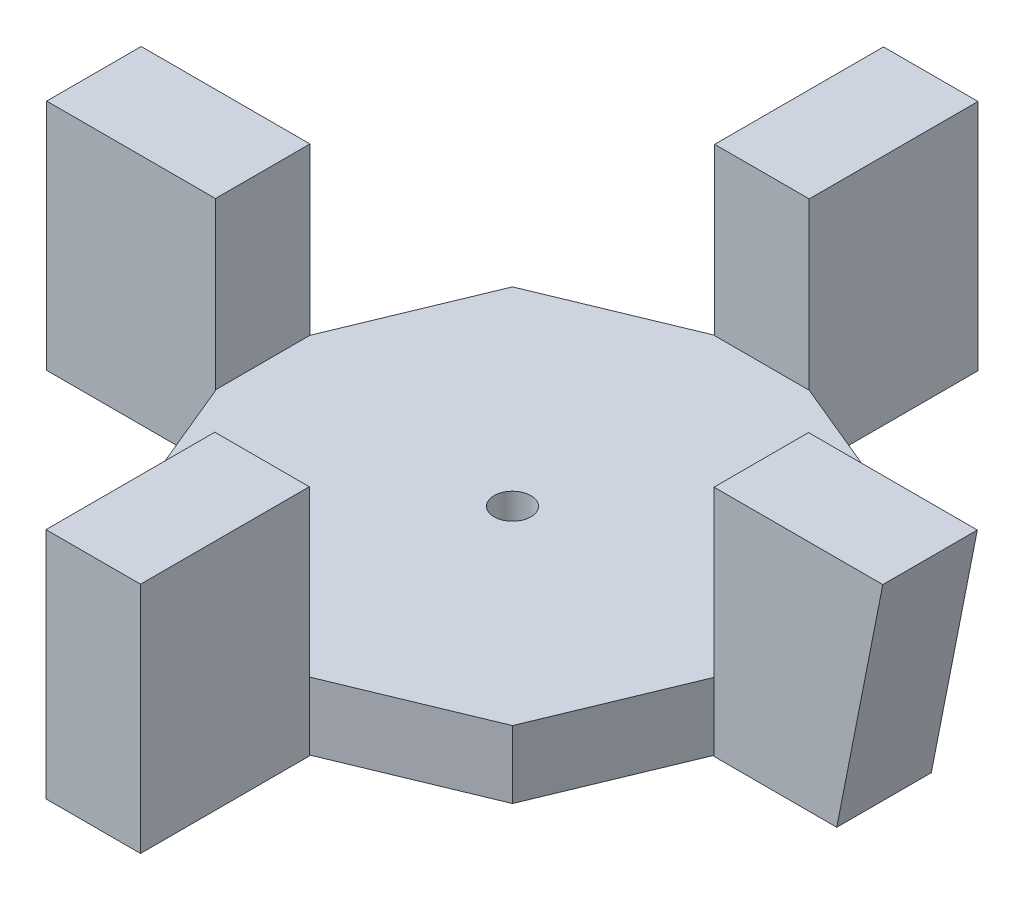
SolidWorks part; units mm, degrees
ref_plane "Front Plane" through (0, 0, 0) normal (0, 0, 1) x (1, 0, 0)
ref_plane "Top Plane" through (0, 0, 0) normal (0, 1, 0) x (1, 0, 0)
ref_plane "Right Plane" through (0, 0, 0) normal (1, 0, 0) x (0, 0, -1)
sketch "Sketch1" plane through (0, 0, 0) normal (0, 1, 0) x (1, 0, 0)
  line L5 (3.85, -20.4) -> (20.3614, -3.9433)
  line L6 (20.3614, 3.7567) -> (3.9046, 20.2681)
  line L13 (-3.7954, 20.2681) -> (-20.3067, 3.8114)
  line L39 (0, 52.6455) -> (0, -55.3936) construction
  line L41 (3.85, -20.4) -> (3.85, -34.15)
  line L42 (3.85, -34.15) -> (-3.85, -34.15)
  line L43 (-3.85, -34.15) -> (-3.85, -20.4)
  line L44 (-71.9201, 0) -> (88.7852, 0) construction
  line L46 (-34.0567, -3.8886) -> (-34.0567, 3.8114)
  line L47 (-20.3067, -3.8886) -> (-34.0567, -3.8886)
  line L48 (-34.0567, 3.8114) -> (-20.3067, 3.8114)
  line L49 (-3.7954, 34.0181) -> (3.9046, 34.0181)
  line L50 (-3.7954, 20.2681) -> (-3.7954, 34.0181)
  line L51 (3.9046, 34.0181) -> (3.9046, 20.2681)
  line L52 (34.1114, 3.7567) -> (34.1114, -3.9433)
  line L53 (20.3614, 3.7567) -> (34.1114, 3.7567)
  line L54 (34.1114, -3.9433) -> (20.3614, -3.9433)
  line L56 (-21.8854, 0) -> (-15.4753, -15.4753)
  line L57 (-15.4753, -15.4753) -> (0, -21.8854)
  line L58 (0, -21.8854) -> (15.4753, -15.4753)
  line L59 (15.4753, -15.4753) -> (21.8854, 0)
  line L60 (21.8854, 0) -> (15.4753, 15.4753)
  line L61 (15.4753, 15.4753) -> (0, 21.8854)
  line L62 (0, 21.8854) -> (-15.4753, 15.4753)
  line L63 (-15.4753, 15.4753) -> (-21.8854, 0)
  line L72 (-20.3067, -3.8886) -> (-3.85, -20.4)
  line L73 (-3.85, -20.4) -> (3.85, -20.4)
  line L74 (20.3614, 3.7567) -> (20.3614, -3.9433)
  line L75 (-3.7954, 20.2681) -> (3.9046, 20.2681)
  line L76 (-20.3067, -3.8886) -> (-20.3067, 3.8114)
  circle A0 centre (0, 0) radius 1.5
  circle A1 centre (0, 0) radius 20.2195 construction
  point P0 (0, 0)
  point P17 (0, 0)
  point P26 (0, 0)
  point P35 (0, 0)
  point P44 (0, 0)
  point P49 (0, -20.4)
  point P57 (0, -34.15)
  point P69 (0.0273, -0.066)
  dimension "D9" = 7.7
  dimension "D1" = 13.75
  dimension "D2" = 3
  dimension "D8" = 4
  dimension "D10" = 4
extrude "Boss-Extrude5" add sketch "Sketch1" along normal mid plane 5.5 contours L72 L56 L57 | L58 L59 L5 | L60 L61 L6 | L76 L56 L72 L57 L73 L58 L5 L59 L74 L60 L6 L75 L13 A0 | L62 L63 L13 L50 | L56 L76 L63 | L47 L76 L56 L63 L48 L46 | L73 L43 L42 L41 L58 L57 | L73 L57 L58 | L60 L74 L59 | L50 L75 L61 L62 | L62 L61 L51 L49 L50 | L53 L74 L60 L59 L54 L52 region at (0, 0, 27.613) region at (3.5918, 0, 19.7751) region at (13.2294, 0, 13.2724) region at (0, 0, 20.8951) region at (27.5924, 0, 0.0985) region at (20.8694, 0, 0) region at (-13.2543, 0, 13.2109) region at (13.2289, 0, -13.185) region at (-27.5643, 0, 0.041) region at (-20.8329, 0, 0) region at (0.058, 0, -27.5448) region at (0.0015, 0, -20.8074) region at (-13.1668, 0, -13.2105)
extrude "Boss-Extrude6" add sketch "Sketch1<10>" along normal blind 16.25 contours L73 L57 L58 | L73 L43 L42 L41 L58 L57 | L47 L76 L56 L63 L48 L46 | L56 L76 L63 | L50 L75 L61 L62 | L62 L61 L51 L49 L50 | L60 L74 L59 | L53 L74 L60 L59 L54 L52 region at (0, 0, 27.613) region at (0, 0, 20.8951) region at (27.5924, 0, 0.0985) region at (20.8694, 0, 0) region at (-27.5643, 0, 0.041) region at (-20.8329, 0, 0) region at (0.058, 0, -27.5448) region at (0.0015, 0, -20.8074)
sketch "Sketch1<10>" plane through (0, 0, 0) normal (0, 1, 0) x (1, 0, 0) same geometry as "Sketch1"
sketch "Sketch3" plane through (0, 0, -3.7567) normal (0, 0, -1) x (-1, 0, 0)
  line L0 (-34.1114, 16.25) -> (-20.3614, 16.25)
  line L1 (-20.3614, 16.25) -> (-20.3614, -2.75)
  line L2 (-20.3614, -2.75) -> (-30.3614, -2.75)
  line L3 (-20.3614, -2.75) -> (-34.1114, -2.75) construction
  line L4 (-30.3614, -2.75) -> (-34.1114, 16.25)
  line L5 (-34.1114, -2.75) -> (-30.3614, -2.75)
  line L6 (-34.1114, -2.75) -> (-34.1114, 16.25)
  line M1 (-34.1114, 16.25) -> (-34.1114, -2.75)
  line M2 (-34.1114, -2.75) -> (-20.3614, -2.75)
  dimension "D1" = 10
extrude "Cut-Extrude2" cut sketch "Sketch3" against normal blind 16.25 contours L4 M2 M1 region at (32.8614, 3.5833, -3.7567)
